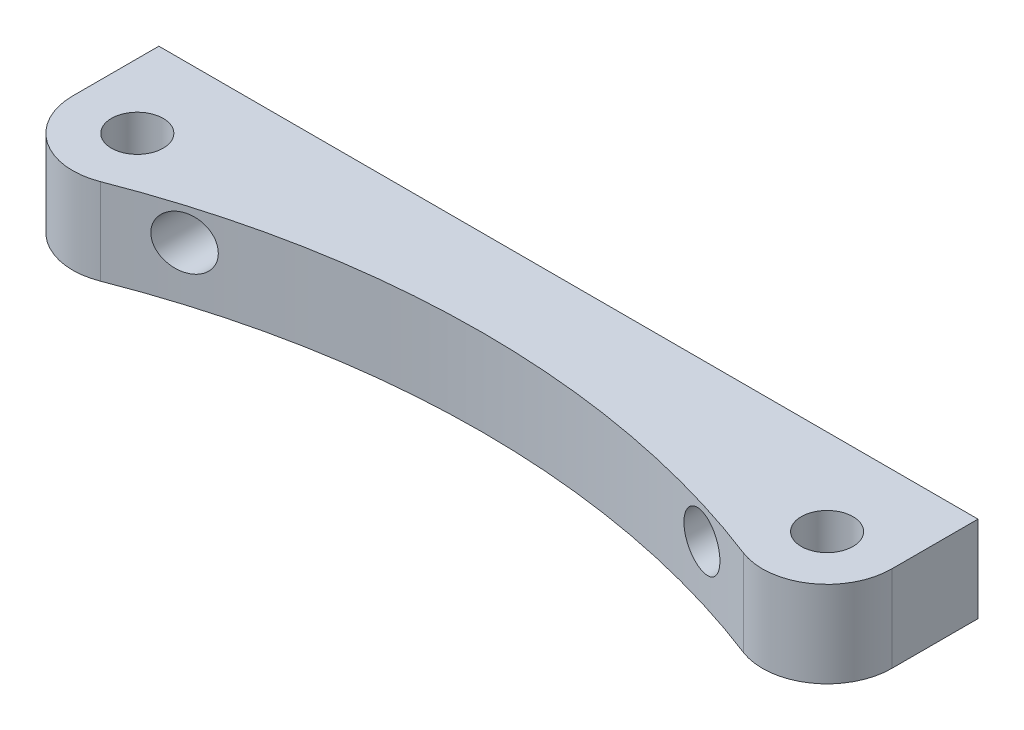
SolidWorks part; units mm, degrees
ref_plane "Front Plane" through (0, 0, 0) normal (0, 0, 1) x (1, 0, 0)
ref_plane "Top Plane" through (0, 0, 0) normal (0, 1, 0) x (1, 0, 0)
ref_plane "Right Plane" through (0, 0, 0) normal (1, 0, 0) x (0, 0, -1)
sketch "Sketch1" plane through (0, 0, 0) normal (0, 1, 0) x (1, 0, 0)
  line L0 (0, 0) -> (50.8, 0) construction
  line L4 (-4.7625, 6.35) -> (-4.7625, 0)
  line L5 (55.5625, 0) -> (55.5625, 6.35)
  line L7 (-4.7625, 6.35) -> (55.5625, 6.35)
  arc A0 (-4.7625, 0) -> (1.7253, -4.439) centre (0, 0) ccw
  arc A1 (49.0747, -4.439) -> (55.5625, 0) centre (50.8, 0) ccw
  circle A2 centre (0, 0) radius 1.905
  circle A3 centre (50.8, 0) radius 1.905
  arc A4 (1.7253, -4.439) -> (49.0747, -4.439) centre (25.4, -65.3521) cw
  point P3 (25.4, 0)
  dimension "D3" = 3.81
  dimension "D4" = 4.7625
  dimension "D1" = 6.35
  dimension "D2" = 50.8
  dimension "D5" = 6.35
extrude "Boss-Extrude1" add sketch "Sketch1" along normal blind 6.35
sketch "Sketch2" plane through (0, 0, -6.35) normal (0, 0, -1) x (-1, 0, 0)
  circle A4 centre (-44.45, 3.9688) radius 1.905
  circle A5 centre (-6.35, 3.9688) radius 1.905
  dimension "D1" = 3.81
extrude "Cut-Extrude1" cut sketch "Sketch2" against normal up to next
